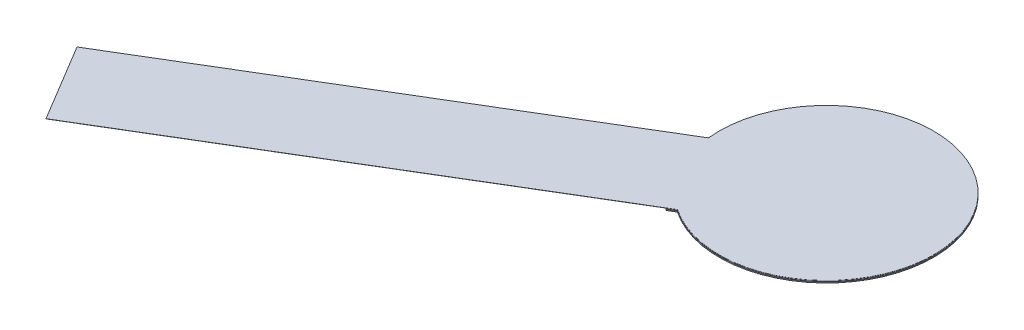
SolidWorks part; units mm, degrees
ref_plane "Front" through (0, 0, 0) normal (0, 0, 1) x (1, 0, 0)
ref_plane "Top" through (0, 0, 0) normal (0, 1, 0) x (1, 0, 0)
ref_plane "Right" through (0, 0, 0) normal (1, 0, 0) x (0, 0, -1)
sketch "草图1" plane through (0, 0, 0) normal (0, 1, 0) x (1, 0, 0)
  line L0 (-29.3743, -0.2148) -> (-22.5736, -0.2148) construction
  line L1 (-3.5542, -5.2622) -> (-26.9062, -19.2935)
  line L3 (-6.3148, -0.6677) -> (-29.6668, -14.699)
  line L4 (0, 0) -> (-28.2865, -16.9963) construction
  line L5 (-26.9062, -19.2935) -> (-29.6668, -14.699)
  line L6 (0, 0) -> (0, -20.3247) construction
  arc A2 (-3.5542, -5.2622) -> (-6.3148, -0.6677) centre (0, 0) ccw
  dimension "D1" = 12.7
  dimension "D4" = 33
  dimension "D5" = 5.36
  dimension "D6" = 59
extrude "PET_all" add sketch "草图1" along normal blind 0.01
sketch "草图2" plane through (0, 0, 0) normal (0, 1, 0) x (1, 0, 0)
  line L0 (-5.0851, -1.3055) -> (-29.0591, -15.7105)
  line L1 (-29.0591, -15.7105) -> (-28.441, -16.7391)
  line L2 (-28.441, -16.7391) -> (-4.3038, -2.236)
  line L3 (0, 0) -> (-28.2865, -16.9963) construction
  line L4 (-3.9948, -2.7503) -> (-28.132, -17.2534)
  line L5 (-28.132, -17.2534) -> (-27.514, -18.282)
  line L6 (-27.514, -18.282) -> (-3.54, -3.877)
  line L7 (0, 0) -> (-28.2865, -16.9963) construction
  line L8 (3.9015, 3.5129) -> (3.6043, 3.2453)
  line L9 (0, 0) -> (7.9526, 4.7784) construction
  line L10 (4.5575, 1.6588) -> (4.9334, 1.7956)
  arc A0 (-3.54, -3.877) -> (4.9334, 1.7956) centre (0, 0) ccw
  arc A1 (-3.9948, -2.7503) -> (4.5575, 1.6588) centre (0, 0) ccw
  arc A2 (3.9015, 3.5129) -> (-5.0851, -1.3055) centre (0, 0) ccw
  arc A3 (3.6043, 3.2453) -> (-4.3038, -2.236) centre (0, 0) ccw
  dimension "D1" = 10.5
  dimension "D2" = 9.7
  dimension "D3" = 33
  dimension "D4" = 0.6
  dimension "D5" = 3
  dimension "D6" = 22
extrude "凸台-拉伸2" add sketch "草图2" against normal blind 0.05 from surface separate body starting at face at (-14.0161, 0, 8.4217)
sketch "草图3" plane through (0, 0, 0) normal (0, 1, 0) x (1, 0, 0)
  line L0 (-2.6109, -4.2948) -> (-4.1551, -1.725)
  line L1 (-2.4395, -4.1918) -> (-3.9836, -1.6219)
  line L2 (-29.6668, -14.699) -> (-26.9062, -19.2935) construction
  line L3 (-4.0693, -1.6735) -> (-3.7287, -2.2404) construction
  line L4 (-4.7316, -2.843) -> (4.7316, 2.843) construction
  line L5 (0, 0) -> (-28.2865, -16.9963) construction
  line L6 (-2.6109, -4.2948) -> (-2.4395, -4.1918)
  line L7 (-4.3085, 0.2778) -> (-1.341, -4.6609)
  line L9 (-1.341, -4.6609) -> (-1.5124, -4.7639)
  line L10 (-4.4799, 0.1748) -> (-1.5124, -4.7639)
  line L11 (-4.3085, 0.2778) -> (-1.5124, -4.7639) construction
  line L12 (-1.341, -4.6609) -> (-4.4799, 0.1748) construction
  line L13 (-4.1243, 1.3304) -> (-0.4218, -4.8316)
  line L14 (-0.4218, -4.8316) -> (-0.5932, -4.9346)
  line L15 (-4.2957, 1.2274) -> (-0.5932, -4.9346)
  line L16 (-4.1243, 1.3304) -> (-0.5932, -4.9346) construction
  line L17 (-0.4218, -4.8316) -> (-4.2957, 1.2274) construction
  line L18 (-3.7904, 2.1338) -> (0.3962, -4.8338)
  line L19 (0.3962, -4.8338) -> (0.2247, -4.9368)
  line L20 (-3.9618, 2.0308) -> (0.2247, -4.9368)
  line L21 (-3.7904, 2.1338) -> (0.2247, -4.9368) construction
  line L22 (0.3962, -4.8338) -> (-3.9618, 2.0308) construction
  line L23 (-3.3638, 2.783) -> (1.1408, -4.7139)
  line L24 (1.1408, -4.7139) -> (0.9694, -4.8169)
  line L25 (-3.5352, 2.68) -> (0.9694, -4.8169)
  line L26 (-3.3638, 2.783) -> (0.9694, -4.8169) construction
  line L27 (1.1408, -4.7139) -> (-3.5352, 2.68) construction
  line L28 (-2.8664, 3.3142) -> (1.825, -4.4935)
  line L29 (1.825, -4.4935) -> (1.6536, -4.5965)
  line L30 (-3.0378, 3.2112) -> (1.6536, -4.5965)
  line L31 (-2.8664, 3.3142) -> (1.6536, -4.5965) construction
  line L32 (1.825, -4.4935) -> (-3.0378, 3.2112) construction
  line L33 (-2.3077, 3.7436) -> (2.4549, -4.1828)
  line L34 (2.4549, -4.1828) -> (2.2835, -4.2858)
  line L35 (-2.4791, 3.6406) -> (2.2835, -4.2858)
  line L36 (-2.3077, 3.7436) -> (2.2835, -4.2858) construction
  line L37 (2.4549, -4.1828) -> (-2.4791, 3.6406) construction
  line L38 (-1.6912, 4.0767) -> (3.0443, -3.8046)
  line L39 (3.0443, -3.8046) -> (2.8729, -3.9076)
  line L40 (-1.8627, 3.9737) -> (2.8729, -3.9076)
  line L41 (-1.6912, 4.0767) -> (2.8729, -3.9076) construction
  line L42 (3.0443, -3.8046) -> (-1.8627, 3.9737) construction
  line L43 (-1.0156, 4.3114) -> (3.5839, -3.3434)
  line L44 (3.5839, -3.3434) -> (3.4124, -3.4464)
  line L45 (-1.1871, 4.2084) -> (3.4124, -3.4464)
  line L46 (-1.0156, 4.3114) -> (3.4124, -3.4464) construction
  line L47 (3.5839, -3.3434) -> (-1.1871, 4.2084) construction
  line L48 (-0.2743, 4.4368) -> (4.0663, -2.7871)
  line L49 (4.0663, -2.7871) -> (3.8948, -2.8901)
  line L50 (-0.4457, 4.3337) -> (3.8948, -2.8901)
  line L51 (-0.2743, 4.4368) -> (3.8948, -2.8901) construction
  line L52 (4.0663, -2.7871) -> (-0.4457, 4.3337) construction
  line L53 (0.5482, 4.4271) -> (4.482, -2.1199)
  line L54 (4.482, -2.1199) -> (4.3106, -2.2229)
  line L55 (0.3767, 4.3241) -> (4.3106, -2.2229)
  line L56 (0.5482, 4.4271) -> (4.3106, -2.2229) construction
  line L57 (4.482, -2.1199) -> (0.3767, 4.3241) construction
  line L58 (1.488, 4.2221) -> (4.8114, -1.3089)
  line L59 (4.8114, -1.3089) -> (4.6399, -1.4119)
  line L60 (1.3166, 4.1191) -> (4.6399, -1.4119)
  line L61 (1.488, 4.2221) -> (4.6399, -1.4119) construction
  line L62 (4.8114, -1.3089) -> (1.3166, 4.1191) construction
  line L63 (2.4339, 4.007) -> (5.0067, -0.2749)
  line L64 (5.0067, -0.2749) -> (4.8353, -0.3779)
  line L65 (2.2624, 3.904) -> (4.8353, -0.3779)
  line L66 (2.4339, 4.007) -> (4.8353, -0.3779) construction
  line L67 (5.0067, -0.2749) -> (2.2624, 3.904) construction
  arc A0 (-4.1551, -1.725) -> (-3.9836, -1.6219) centre (-4.0693, -1.6735) cw
  arc A1 (-4.3085, 0.2778) -> (-4.4799, 0.1748) centre (-4.3942, 0.2263) ccw
  arc A2 (-3.9948, -2.7503) -> (4.5575, 1.6588) centre (0, 0) ccw construction
  arc A3 (-3.9948, -2.7503) -> (4.5575, 1.6588) centre (0, 0) ccw construction
  arc A5 (3.8573, 2.3177) -> (-3.8573, -2.3177) centre (0, 0) ccw construction
  arc A6 (-4.1243, 1.3304) -> (-4.2957, 1.2274) centre (-4.21, 1.2789) ccw
  arc A7 (-3.7904, 2.1338) -> (-3.9618, 2.0308) centre (-3.8761, 2.0823) ccw
  arc A8 (-3.3638, 2.783) -> (-3.5352, 2.68) centre (-3.4495, 2.7315) ccw
  arc A9 (-2.8664, 3.3142) -> (-3.0378, 3.2112) centre (-2.9521, 3.2627) ccw
  arc A10 (-2.3077, 3.7436) -> (-2.4791, 3.6406) centre (-2.3934, 3.6921) ccw
  arc A11 (-1.6912, 4.0767) -> (-1.8627, 3.9737) centre (-1.777, 4.0252) ccw
  arc A12 (-1.0156, 4.3114) -> (-1.1871, 4.2084) centre (-1.1013, 4.2599) ccw
  arc A13 (-0.2743, 4.4368) -> (-0.4457, 4.3337) centre (-0.36, 4.3852) ccw
  arc A14 (0.5482, 4.4271) -> (0.3767, 4.3241) centre (0.4624, 4.3756) ccw
  arc A15 (1.488, 4.2221) -> (1.3166, 4.1191) centre (1.4023, 4.1706) ccw
  arc A16 (2.4339, 4.007) -> (2.2624, 3.904) centre (2.3481, 3.9555) ccw
  point P18 (-2.9104, -2.2431)
  dimension "D2" = 9
  dimension "D3" = 0.1
  dimension "D1" = 4.35
  dimension "D4" = 0.2
  dimension "D5" = 0.7
  dimension "D6" = 1.4
  dimension "D7" = 2.1
  dimension "D8" = 2.8
  dimension "D9" = 3.5
  dimension "D10" = 4.2
  dimension "D11" = 4.9
  dimension "D12" = 5.6
  dimension "D13" = 6.3
  dimension "D14" = 7
  dimension "D15" = 7.7
  dimension "D16" = 8.4
extrude "凸台-拉伸3" add sketch "草图3" against normal blind 0.05 from surface starting at face at (-14.0161, 0, 8.4217)
sketch "草图8" plane through (0, 0, 0) normal (0, 1, 0) x (1, 0, 0)
  line L0 (2.6593, 4.2663) -> (4.0699, 1.9188)
  line L1 (2.4879, 4.1633) -> (3.8984, 1.8157)
  line L2 (3.9841, 1.8672) -> (3.7516, 2.2542) construction
  line L3 (4.7845, 2.8748) -> (-4.7845, -2.8748) construction
  line L4 (2.6593, 4.2663) -> (2.4879, 4.1633)
  line L5 (4.3107, -0.2295) -> (1.3789, 4.6499)
  line L6 (1.3789, 4.6499) -> (1.5503, 4.7529)
  line L7 (4.4821, -0.1265) -> (1.5503, 4.7529)
  line L8 (4.3107, -0.2295) -> (1.5503, 4.7529) construction
  line L9 (1.3789, 4.6499) -> (4.4821, -0.1265) construction
  line L10 (4.1347, -1.2957) -> (0.4548, 4.8286)
  line L11 (0.4548, 4.8286) -> (0.6262, 4.9316)
  line L12 (4.3061, -1.1927) -> (0.6262, 4.9316)
  line L13 (4.1347, -1.2957) -> (0.6262, 4.9316) construction
  line L14 (0.4548, 4.8286) -> (4.3061, -1.1927) construction
  line L15 (3.8051, -2.1062) -> (-0.3663, 4.8361)
  line L16 (-0.3663, 4.8361) -> (-0.1949, 4.9392)
  line L17 (3.9765, -2.0032) -> (-0.1949, 4.9392)
  line L18 (3.8051, -2.1062) -> (-0.1949, 4.9392) construction
  line L19 (-0.3663, 4.8361) -> (3.9765, -2.0032) construction
  line L20 (3.3815, -2.7604) -> (-1.1135, 4.7205)
  line L21 (-1.1135, 4.7205) -> (-0.942, 4.8235)
  line L22 (3.5529, -2.6574) -> (-0.942, 4.8235)
  line L23 (3.3815, -2.7604) -> (-0.942, 4.8235) construction
  line L24 (-1.1135, 4.7205) -> (3.5529, -2.6574) construction
  line L25 (2.8865, -3.2958) -> (-1.7999, 4.5037)
  line L26 (-1.7999, 4.5037) -> (-1.6284, 4.6067)
  line L27 (3.058, -3.1928) -> (-1.6284, 4.6067)
  line L28 (2.8865, -3.2958) -> (-1.6284, 4.6067) construction
  line L29 (-1.7999, 4.5037) -> (3.058, -3.1928) construction
  line L30 (2.3302, -3.7289) -> (-2.4318, 4.1963)
  line L31 (-2.4318, 4.1963) -> (-2.2604, 4.2993)
  line L32 (2.5016, -3.6259) -> (-2.2604, 4.2993)
  line L33 (2.3302, -3.7289) -> (-2.2604, 4.2993) construction
  line L34 (-2.4318, 4.1963) -> (2.5016, -3.6259) construction
  line L35 (1.7159, -4.0658) -> (-3.0226, 3.8204)
  line L36 (-3.0226, 3.8204) -> (-2.8512, 3.9234)
  line L37 (1.8873, -3.9628) -> (-2.8512, 3.9234)
  line L38 (1.7159, -4.0658) -> (-2.8512, 3.9234) construction
  line L39 (-3.0226, 3.8204) -> (1.8873, -3.9628) construction
  line L40 (1.0426, -4.3044) -> (-3.5642, 3.3627)
  line L41 (-3.5642, 3.3627) -> (-3.3928, 3.4657)
  line L42 (1.214, -4.2014) -> (-3.3928, 3.4657)
  line L43 (1.0426, -4.3044) -> (-3.3928, 3.4657) construction
  line L44 (-3.5642, 3.3627) -> (1.214, -4.2014) construction
  line L45 (0.304, -4.4342) -> (-4.049, 2.8103)
  line L46 (-4.049, 2.8103) -> (-3.8775, 2.9133)
  line L47 (0.4754, -4.3312) -> (-3.8775, 2.9133)
  line L48 (0.304, -4.4342) -> (-3.8775, 2.9133) construction
  line L49 (-4.049, 2.8103) -> (0.4754, -4.3312) construction
  line L50 (-0.5149, -4.4305) -> (-4.4675, 2.1478)
  line L51 (-4.4675, 2.1478) -> (-4.2961, 2.2508)
  line L52 (-0.3434, -4.3275) -> (-4.2961, 2.2508)
  line L53 (-0.5149, -4.4305) -> (-4.2961, 2.2508) construction
  line L54 (-4.4675, 2.1478) -> (-0.3434, -4.3275) construction
  line L55 (-1.449, -4.235) -> (-4.8008, 1.3433)
  line L56 (-4.8008, 1.3433) -> (-4.6293, 1.4463)
  line L57 (-1.2776, -4.132) -> (-4.6293, 1.4463)
  line L58 (-1.449, -4.235) -> (-4.6293, 1.4463) construction
  line L59 (-4.8008, 1.3433) -> (-1.2776, -4.132) construction
  line L60 (-2.3857, -4.0353) -> (-5.0029, 0.3206)
  line L61 (-5.0029, 0.3206) -> (-4.8315, 0.4236)
  line L62 (-2.2142, -3.9322) -> (-4.8315, 0.4236)
  line L63 (-2.3857, -4.0353) -> (-4.8315, 0.4236) construction
  line L64 (-5.0029, 0.3206) -> (-2.2142, -3.9322) construction
  line L65 (-26.9062, -19.2935) -> (-29.6668, -14.699) construction
  arc A0 (4.0699, 1.9188) -> (3.8984, 1.8157) centre (3.9841, 1.8672) cw
  arc A1 (4.3107, -0.2295) -> (4.4821, -0.1265) centre (4.3964, -0.178) ccw
  arc A2 (3.6043, 3.2453) -> (-4.3038, -2.236) centre (0, 0) ccw construction
  arc A3 (-3.8573, -2.3177) -> (3.8573, 2.3177) centre (0, 0) ccw construction
  arc A4 (4.1347, -1.2957) -> (4.3061, -1.1927) centre (4.2204, -1.2442) ccw
  arc A5 (3.8051, -2.1062) -> (3.9765, -2.0032) centre (3.8908, -2.0547) ccw
  arc A6 (3.3815, -2.7604) -> (3.5529, -2.6574) centre (3.4672, -2.7089) ccw
  arc A7 (2.8865, -3.2958) -> (3.058, -3.1928) centre (2.9723, -3.2443) ccw
  arc A8 (2.3302, -3.7289) -> (2.5016, -3.6259) centre (2.4159, -3.6774) ccw
  arc A9 (1.7159, -4.0658) -> (1.8873, -3.9628) centre (1.8016, -4.0143) ccw
  arc A10 (1.0426, -4.3044) -> (1.214, -4.2014) centre (1.1283, -4.2529) ccw
  arc A11 (0.304, -4.4342) -> (0.4754, -4.3312) centre (0.3897, -4.3827) ccw
  arc A12 (-0.5149, -4.4305) -> (-0.3434, -4.3275) centre (-0.4292, -4.379) ccw
  arc A13 (-1.449, -4.235) -> (-1.2776, -4.132) centre (-1.3633, -4.1835) ccw
  arc A14 (-2.3857, -4.0353) -> (-2.2142, -3.9322) centre (-2.2999, -3.9837) ccw
  arc A15 (3.6043, 3.2453) -> (-4.3038, -2.236) centre (0, 0) ccw construction
  point P13 (2.9305, 2.2617)
  dimension "D1" = 9
  dimension "D2" = 0.1
  dimension "D4" = 0.2
  dimension "D5" = 0.7
  dimension "D6" = 1.4
  dimension "D7" = 2.1
  dimension "D8" = 2.8
  dimension "D9" = 3.5
  dimension "D10" = 4.2
  dimension "D11" = 4.9
  dimension "D12" = 5.6
  dimension "D13" = 6.3
  dimension "D14" = 7
  dimension "D15" = 7.7
  dimension "D16" = 8.4
extrude "凸台-拉伸5" add sketch "草图8" against normal blind 0.05 from surface starting at face at (-14.0161, 0, 8.4217)
sketch "草图6" plane through (0, 0, 0) normal (0, 1, 0) x (1, 0, 0)
  line L0 (-6.3148, -0.6677) -> (-6.7376, -0.9218)
  line L1 (-6.3148, -0.6677) -> (-29.6668, -14.699) construction
  line L2 (-6.7376, -0.9218) -> (-3.977, -5.5162)
  line L3 (-26.9062, -19.2935) -> (-3.5542, -5.2622) construction
  line L4 (-3.977, -5.5162) -> (-3.5542, -5.2622)
  arc A0 (-3.5542, -5.2622) -> (-6.3148, -0.6677) centre (0, 0) ccw construction
  arc A1 (-3.5542, -5.2622) -> (-6.3148, -0.6677) centre (0, 0) ccw
  dimension "D1" = 6.25
extrude "FSR" add sketch "草图6" against normal blind 0.01 from offset 0.06 separate body offset against normal yes
sketch "草图10" plane through (0, 0, 0) normal (0, 1, 0) x (1, 0, 0)
  line L0 (-6.3148, -0.6677) -> (-6.7376, -0.9218)
  line L1 (-6.7376, -0.9218) -> (-5.4603, -3.0476)
  line L2 (-28.132, -17.2534) -> (-3.9948, -2.7503) construction
  line L3 (-6.7376, -0.9218) -> (-3.977, -5.5162) construction
  line L5 (-5.2543, -3.3904) -> (-3.977, -5.5162)
  line L7 (-26.9062, -19.2935) -> (-3.5542, -5.2622) construction
  line L11 (-3.977, -5.5162) -> (-3.5542, -5.2622)
  line L12 (-5.4603, -3.0476) -> (-3.9564, -2.1439)
  line L13 (-5.2543, -3.3904) -> (-3.7504, -2.4868)
  line L14 (-4.3038, -2.236) -> (-28.441, -16.7391) construction
  arc A0 (-3.7504, -2.4868) -> (-3.9564, -2.1439) centre (0, 0) ccw
  arc A1 (-3.5542, -5.2622) -> (-6.3148, -0.6677) centre (0, 0) ccw construction
  arc A2 (-3.5542, -5.2622) -> (-6.3148, -0.6677) centre (0, 0) ccw
  dimension "D1" = 4.5
  dimension "D2" = 0.1
  dimension "D3" = 0.1
extrude "垫片" add sketch "草图10" against normal blind 0.01 from surface separate body starting at face at (-1.0527, -0.05, 0.1453)
sketch "草图11" plane through (0, 0, 0) normal (0, 1, 0) x (1, 0, 0)
  line L12 (-6.1814, -1.8475) -> (-5.4603, -3.0476)
  line L13 (-5.2543, -3.3904) -> (-28.1835, -17.1677)
  line L14 (-5.2543, -3.3904) -> (-4.5332, -4.5905)
  line L15 (-6.7376, -0.9218) -> (-5.4603, -3.0476) construction
  line L16 (-4.5332, -4.5905) -> (-27.4625, -18.3677)
  line L17 (-5.4603, -3.0476) -> (-28.3895, -16.8248)
  line L18 (-6.1814, -1.8475) -> (-29.1106, -15.6248)
  line L19 (-29.6668, -14.699) -> (-26.9062, -19.2935) construction
  line L20 (-29.1106, -15.6248) -> (-28.3895, -16.8248)
  line L21 (-28.1835, -17.1677) -> (-27.4625, -18.3677)
  line L22 (-28.2865, -16.9963) -> (0, 0) construction
  line L23 (-29.6668, -14.699) -> (-26.9062, -19.2935) construction
  line L24 (-28.132, -17.2534) -> (-3.9948, -2.7503) construction
  line L25 (-3.54, -3.877) -> (-27.514, -18.282) construction
  dimension "D1" = 0.1
  dimension "D2" = 0.1
extrude "尾部" add sketch "草图11" against normal blind 0.11 from offset 0.01 separate body offset against normal yes
sketch "草图12" plane through (0, 0, 0) normal (0, 1, 0) x (1, 0, 0)
  line L0 (-26.9062, -19.2935) -> (-3.5542, -5.2622) construction
  line L1 (-6.3148, -0.6677) -> (-29.6668, -14.699) construction
  line L2 (-6.7376, -0.9218) -> (-3.977, -5.5162) construction
  line L3 (-3.977, -5.5162) -> (-3.5542, -5.2622)
  line L4 (-6.3148, -0.6677) -> (-6.7376, -0.9218)
  line L5 (-6.7376, -0.9218) -> (-3.977, -5.5162)
  arc A0 (-3.5542, -5.2622) -> (-6.3148, -0.6677) centre (0, 0) ccw construction
  arc A1 (-3.5542, -5.2622) -> (-6.3148, -0.6677) centre (0, 0) ccw
extrude "PET_touch" add sketch "草图12" against normal blind 0.05 from surface separate body starting at face at (-2.5515, -0.07, 1.5331)
equation "\"。7\"=0.750295"
